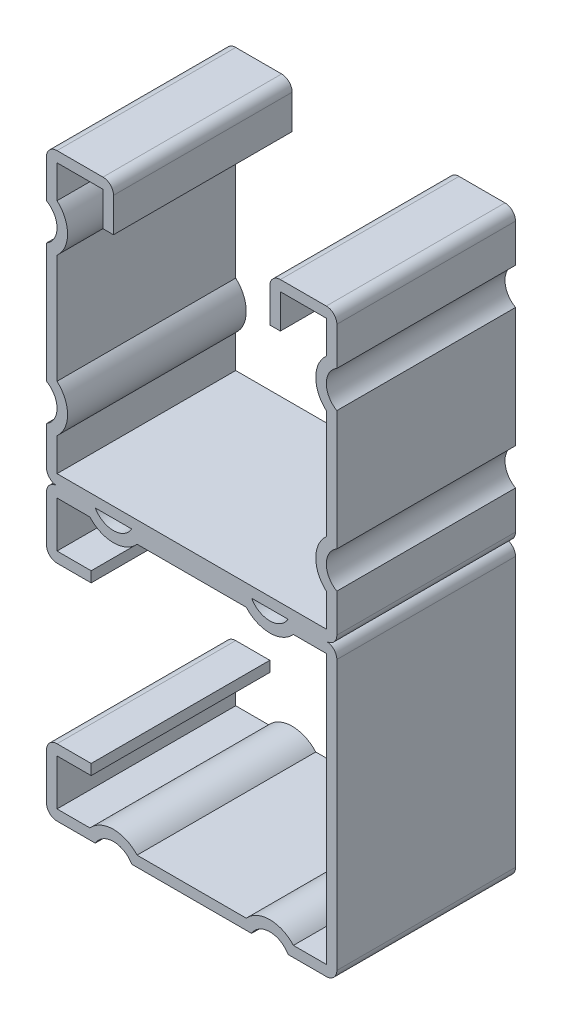
SolidWorks part; units mm, degrees
note: '?' marks a value the reader was unsure of.
ref_plane "Plane1" through (0, 0, 0) normal (0, 0, 1) x (1, 0, 0)
ref_plane "Plane2" through (0, 0, 0) normal (0, 1, 0) x (1, 0, 0)
ref_plane "Plane3" through (0, 0, 0) normal (1, 0, 0) x (0, 0, -1)
sketch "Sketch1" plane through (0, 0, 0) normal (0, 0, 1) x (1, 0, 0)
  line L0 (-41.275, 39.7764) -> (-41.275, 34.3457)
  line L1 (-41.275, 29.1543) -> (-41.275, 12.1207)
  line L2 (-39.7764, 0) -> (-1.4986, 0)
  line L3 (0, 1.4986) -> (0, 6.9293)
  line L4 (0, 34.3457) -> (0, 39.7764)
  line L5 (-1.4986, 41.275) -> (-8.0264, 41.275)
  line L6 (-9.525, 39.7764) -> (-9.525, 34.925)
  line L7 (-39.7764, 41.275) -> (-33.2486, 41.275)
  line L8 (-31.75, 39.7764) -> (-31.75, 34.925)
  line L9 (-1.4986, 6.174) -> (-1.4986, 35.101) construction
  line L10 (-39.7764, 35.101) -> (-39.7764, 6.174) construction
  line L11 (-33.2486, 39.7764) -> (-33.2486, 34.925)
  line L12 (-39.7764, 39.7764) -> (-33.2486, 39.7764)
  line L13 (-39.7764, 39.7764) -> (-39.7764, 35.101)
  line L14 (-39.7764, 28.399) -> (-39.7764, 12.876)
  line L15 (-39.7764, 1.4986) -> (-1.4986, 1.4986)
  line L16 (-1.4986, 1.4986) -> (-1.4986, 6.174)
  line L17 (-1.4986, 35.101) -> (-1.4986, 39.7764)
  line L18 (-1.4986, 39.7764) -> (-8.0264, 39.7764)
  line L19 (-8.0264, 39.7764) -> (-8.0264, 34.925)
  line L20 (-33.2486, 34.925) -> (-31.75, 34.925)
  line L21 (-9.525, 34.925) -> (-8.0264, 34.925)
  line L22 (-10.16, 20.6375) -> (12.7, 20.6375) construction
  line L23 (-41.275, 6.9293) -> (-41.275, 1.4986)
  line L24 (-39.7764, 6.174) -> (-39.7764, 1.4986)
  line L25 (0, 12.1207) -> (0, 29.1543)
  line L26 (-1.4986, 12.876) -> (-1.4986, 28.399)
  arc A0 (0, 34.3457) -> (0, 29.1543) centre (1.4986, 31.75) ccw
  arc A1 (-41.275, 29.1543) -> (-41.275, 34.3457) centre (-42.7736, 31.75) ccw
  arc A2 (-33.2486, 41.275) -> (-31.75, 39.7764) centre (-33.2486, 39.7764) cw
  arc A3 (-41.275, 39.7764) -> (-39.7764, 41.275) centre (-39.7764, 39.7764) cw
  arc A4 (-39.7764, 0) -> (-41.275, 1.4986) centre (-39.7764, 1.4986) cw
  arc A5 (0, 1.4986) -> (-1.4986, 0) centre (-1.4986, 1.4986) cw
  arc A6 (-1.4986, 41.275) -> (0, 39.7764) centre (-1.4986, 39.7764) cw
  arc A7 (-9.525, 39.7764) -> (-8.0264, 41.275) centre (-8.0264, 39.7764) cw
  arc A8 (-39.7764, 28.399) -> (-39.7764, 35.101) centre (-42.7736, 31.75) ccw
  arc A9 (-1.4986, 35.101) -> (-1.4986, 28.399) centre (1.4986, 31.75) ccw
  arc A10 (0, 6.9293) -> (0, 12.1207) centre (1.4986, 9.525) cw
  arc A11 (-1.4986, 6.174) -> (-1.4986, 12.876) centre (1.4986, 9.525) cw
  arc A12 (-39.7764, 12.876) -> (-39.7764, 6.174) centre (-42.7736, 9.525) cw
  arc A13 (-41.275, 12.1207) -> (-41.275, 6.9293) centre (-42.7736, 9.525) cw
  dimension "D9" = 2.9972
  dimension "D10" = 2.9972
  dimension "D6" = 22.225
  dimension "D2" = 9.525
  dimension "D1" = 41.275
  dimension "D3" = 20.6375
extrude "Base-Extrude" add sketch "Sketch1" along normal mid plane 25.4
ref_axis "Axis1" through (0, 0, -50) along (0, 0, 1)?
pattern_circular "CirPattern1" count 2 every 90 about axis through (0, 0, 0) along (0, 0, 1) of "Base-Extrude"
equation "\"D6@Sketch1\" = \"Width@Sketch1\" - 2 * \"edge@Sketch1\""
equation "\"D10@Sketch1\" = 2 * \"gauge@Sketch1\""
equation "\"D9@Sketch1\" = \"D10@Sketch1\""
equation "\"D2@Sketch1\" = \"edge@Sketch1\""
